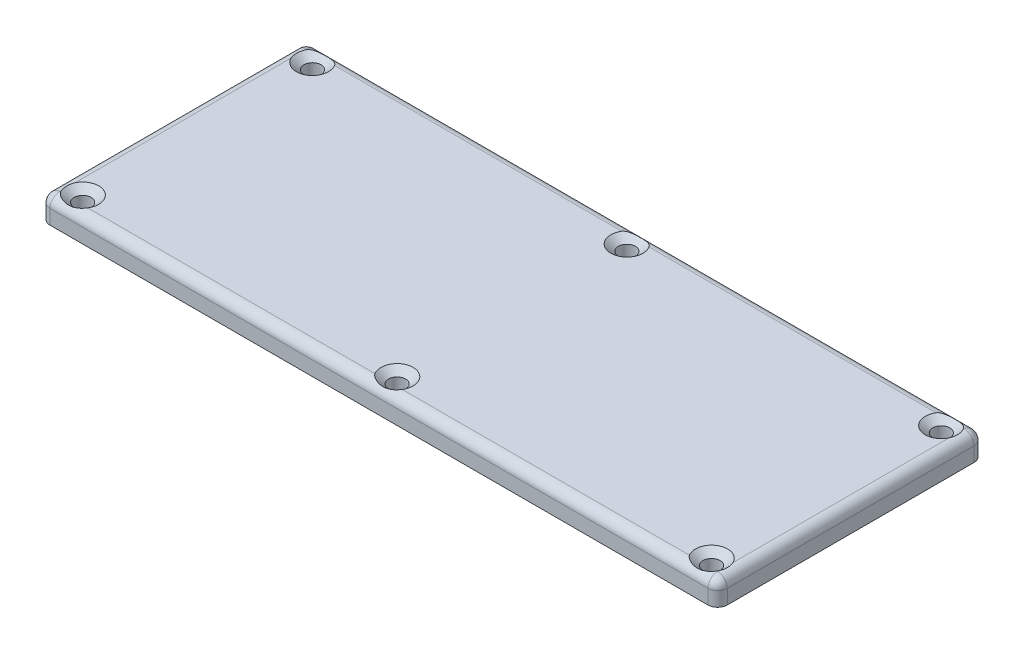
SolidWorks part; units mm, degrees
ref_plane "Front Plane" through (0, 0, 0) normal (0, 0, 1) x (1, 0, 0)
ref_plane "Top Plane" through (0, 0, 0) normal (0, 1, 0) x (1, 0, 0)
ref_plane "Right Plane" through (0, 0, 0) normal (1, 0, 0) x (0, 0, -1)
sketch "Sketch1" plane through (0, 0, 0) normal (0, 1, 0) x (1, 0, 0)
  line L1 (0, 0) -> (177.8, 0)
  line L2 (0, 0) -> (0, 69.85)
  line L3 (0, 69.85) -> (177.8, 69.85)
  line L4 (177.8, 0) -> (177.8, 69.85)
  dimension "D1" = 177.8
  dimension "D2" = 69.85
extrude "Boss-Extrude1" add sketch "Sketch1" along normal blind 6.35
hole_wizard "CSK for #8 Flat Head Machine Screw (100)1" positions "Sketch2" profile "Sketch3" countersink size "#8" standard "ANSI Inch"
sketch "Sketch2" plane through (0, 6.35, 0) normal (0, 1, 0) x (1, 0, 0)
  line L0 (0, 69.85) -> (0, 0) construction
  line L1 (177.8, 69.85) -> (0, 69.85) construction
  line L2 (0, 0) -> (177.8, 0) construction
  line L3 (177.8, 0) -> (177.8, 69.85) construction
  line L4 (88.9, 69.85) -> (88.9, -10.1841) construction
  point P0 (88.9, 65.0875)
  point P2 (6.35, 65.0875)
  point P4 (171.45, 65.0875)
  point P6 (171.45, 4.7625)
  point P8 (88.9, 4.7625)
  point P10 (6.35, 4.7625)
  dimension "D1" = 6.35
  dimension "D2" = 4.7625
  dimension "D3" = 4.7625
  dimension "D4" = 6.35
sketch "Sketch3" plane through (88.9, 6.35, -65.0875) normal (1, 0, 0) x (0, 0, 1)
  line L0 (0, 0) -> (0, 14.0507)
  line L1 (0, 14.0507) -> (2.2479, 12.7)
  line L2 (2.2479, 12.7) -> (2.2479, 1.6518)
  line L3 (2.2479, 1.6518) -> (4.2164, 0)
  line L5 (4.2164, 0) -> (0, 0)
  line L6 (-2.2479, 1.6518) -> (-4.2164, 0) construction
  line L10 (0, 14.0507) -> (-2.2479, 12.7) construction
  line L11 (0, -6.35) -> (0, 107.95) construction
  dimension "Hole Dia." = 4.4958
  dimension "Hole Depth" = 12.7
  dimension "Near C'Sink Dia." = 8.4328
  dimension "Near C'Sink Angle" = 100
  dimension "Drill Angle" = 118
fillet "Fillet1" radius 2.54 8 edges at (177.8, 3.175, 0) (177.8, 3.175, -69.85) (0, 3.175, -69.85) (0, 3.175, 0) (0, 6.35, -34.925) (177.8, 6.35, -34.925) (88.9, 6.35, -69.85) (88.9, 6.35, 0)
